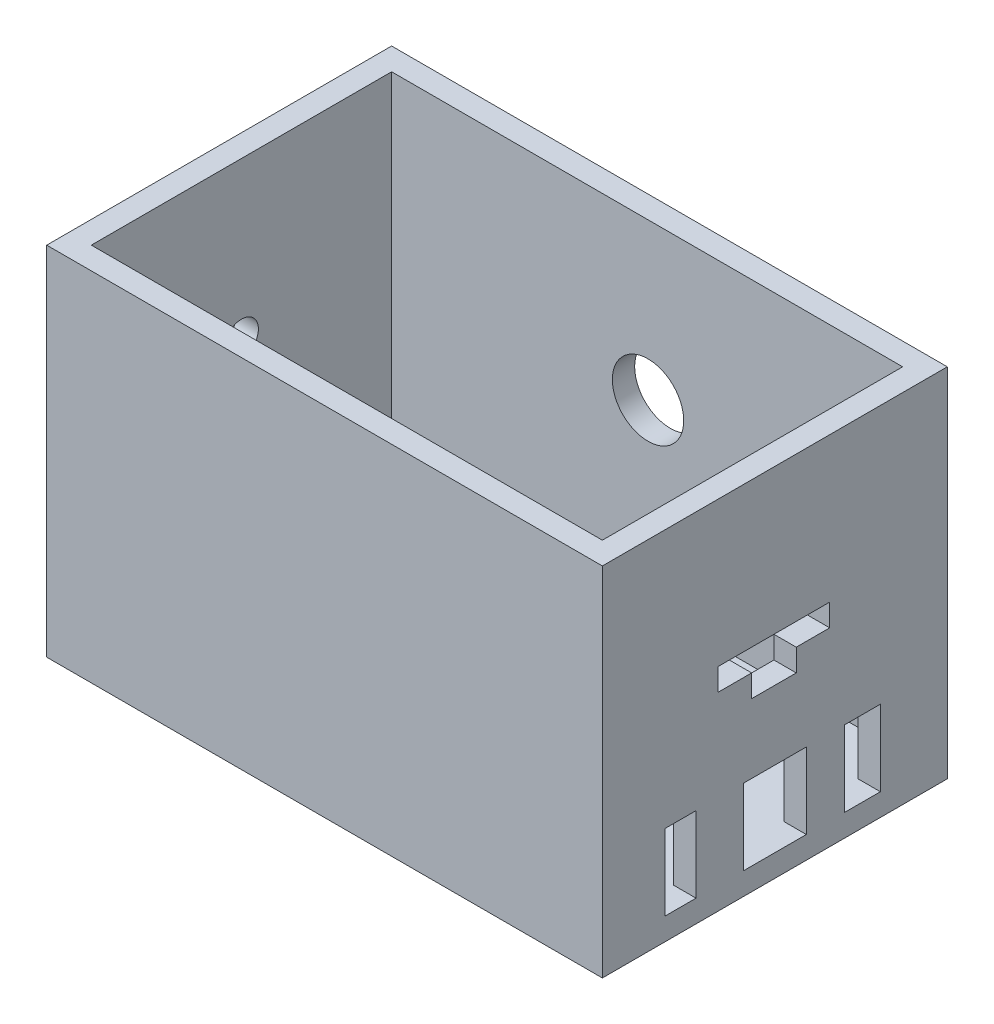
SolidWorks part; units mm, degrees
ref_plane "Front Plane" through (0, 0, 0) normal (0, 0, 1) x (1, 0, 0)
ref_plane "Top Plane" through (0, 0, 0) normal (0, 1, 0) x (1, 0, 0)
ref_plane "Right Plane" through (0, 0, 0) normal (1, 0, 0) x (0, 0, -1)
sketch "Sketch1" plane through (0, 0, 0) normal (0, 1, 0) x (1, 0, 0)
  line L1 (-79.1, 49.1) -> (79.1, 49.1)
  line L2 (-79.1, 49.1) -> (-79.1, -49.1)
  line L3 (-79.1, -49.1) -> (79.1, -49.1)
  line L4 (79.1, 49.1) -> (79.1, -49.1)
  line L5 (-79.1, 49.1) -> (79.1, -49.1) construction
  line L6 (-79.1, -49.1) -> (79.1, 49.1) construction
  point P0 (0, 0)
  dimension "D1" = 158.2
  dimension "D2" = 98.2
extrude "Boss-Extrude1" add sketch "Sketch1" along normal blind 6.35
sketch "Sketch2" plane through (0, 0, 49.1) normal (0, 0, 1) x (1, 0, 0)
  line L1 (-79.1, 101.6) -> (79.1, 101.6)
  line L2 (-79.1, 101.6) -> (-79.1, 6.35)
  line L3 (-79.1, 6.35) -> (79.1, 6.35)
  line L4 (79.1, 101.6) -> (79.1, 6.35)
  line L5 (-79.1, 101.6) -> (79.1, 6.35) construction
  line L6 (-79.1, 6.35) -> (79.1, 101.6) construction
  point P0 (0, 53.975)
  dimension "D1" = 95.25
extrude "Boss-Extrude2" add sketch "Sketch2" against normal blind 6.35
sketch "Sketch3" plane through (-79.1, 0, 0) normal (-1, 0, 0) x (0, 0, 1)
  line L1 (-42.75, 101.6) -> (42.75, 101.6)
  line L2 (-42.75, 101.6) -> (-42.75, 6.35)
  line L3 (-42.75, 6.35) -> (42.75, 6.35)
  line L4 (42.75, 101.6) -> (42.75, 6.35)
  line L5 (-42.75, 101.6) -> (42.75, 6.35) construction
  line L6 (-42.75, 6.35) -> (42.75, 101.6) construction
  point P0 (0, 53.975)
  dimension "D1" = 95.25
extrude "Boss-Extrude3" add sketch "Sketch3" against normal blind 6.35
sketch "Sketch4" plane through (0, 0, -49.1) normal (0, 0, -1) x (-1, 0, 0)
  line L1 (-79.1, 101.6) -> (79.1, 101.6)
  line L2 (-79.1, 101.6) -> (-79.1, 6.35)
  line L3 (-79.1, 6.35) -> (79.1, 6.35)
  line L4 (79.1, 101.6) -> (79.1, 6.35)
  line L5 (-79.1, 101.6) -> (79.1, 6.35) construction
  line L6 (-79.1, 6.35) -> (79.1, 101.6) construction
  point P0 (0, 53.975)
  dimension "D1" = 95.25
extrude "Boss-Extrude4" add sketch "Sketch4" against normal blind 6.35
sketch "Sketch5" plane through (79.1, 0, 0) normal (1, 0, 0) x (0, 0, -1)
  line L0 (42.75, 101.6) -> (42.75, 6.35) construction
  line L1 (-42.75, 27.94) -> (42.75, 27.94)
  line L2 (-42.75, 27.94) -> (-42.75, 101.6)
  line L3 (-42.75, 101.6) -> (42.75, 101.6)
  line L4 (42.75, 27.94) -> (42.75, 101.6)
  line L5 (-42.75, 27.94) -> (42.75, 101.6) construction
  line L6 (-42.75, 101.6) -> (42.75, 27.94) construction
  line L7 (42.75, 101.6) -> (42.75, 6.35) construction
  line L8 (42.75, 101.6) -> (49.1, 101.6) construction
  point P0 (0, 64.77)
  dimension "D1" = 73.66
  dimension "D2" = 0
extrude "Boss-Extrude5" add sketch "Sketch5" against normal blind 6.35
sketch "Sketch6" plane through (79.1, 0, 0) normal (1, 0, 0) x (0, 0, -1)
  line L0 (-42.75, 27.94) -> (42.75, 27.94) construction
  line L1 (-22.43, 27.94) -> (-8.968, 27.94)
  line L2 (-22.43, 27.94) -> (-22.43, 6.35)
  line L3 (-22.43, 6.35) -> (-8.968, 6.35)
  line L4 (-8.968, 27.94) -> (-8.968, 6.35)
  line L5 (-42.75, 6.35) -> (42.75, 6.35) construction
  line L6 (42.75, 6.35) -> (-42.75, 6.35) construction
  line L7 (8.968, 27.94) -> (19.89, 27.94)
  line L8 (8.968, 27.94) -> (8.968, 6.35)
  line L9 (8.968, 6.35) -> (19.89, 6.35)
  line L10 (19.89, 27.94) -> (19.89, 6.35)
  line L11 (-42.75, 6.35) -> (-42.75, 27.94) construction
  line L12 (42.75, 27.94) -> (42.75, 6.35) construction
  line L14 (-42.75, 27.94) -> (-31.32, 27.94)
  line L15 (-42.75, 27.94) -> (-42.75, 6.35)
  line L16 (-42.75, 6.35) -> (-31.32, 6.35)
  line L17 (-31.32, 27.94) -> (-31.32, 6.35)
  line L18 (42.75, 27.94) -> (30.05, 27.94)
  line L19 (42.75, 27.94) -> (42.75, 6.35)
  line L20 (42.75, 6.35) -> (30.05, 6.35)
  line L21 (30.05, 27.94) -> (30.05, 6.35)
  dimension "D1" = 13.462
  dimension "D2" = 10.922
  dimension "D3" = 20.32
  dimension "D4" = 22.86
  dimension "D5" = 0
  dimension "D6" = 11.43
  dimension "D7" = 12.7
  dimension "D8" = 17.936
extrude "Boss-Extrude6" add sketch "Sketch6" against normal blind 6.35
sketch "Çizim2" plane through (79.1, 0, 0) normal (1, 0, 0) x (0, 0, -1)
  line L0 (-49.1, 0) -> (49.1, 0) construction
  line L1 (-16.125, 60.325) -> (15.625, 60.325)
  line L2 (-16.125, 60.325) -> (-16.125, 53.975)
  line L3 (-16.125, 53.975) -> (-6.6, 53.975)
  line L4 (15.625, 60.325) -> (15.625, 53.975)
  line L5 (-16.125, 60.325) -> (15.625, 53.975) construction
  line L6 (-16.125, 53.975) -> (15.625, 60.325) construction
  line L7 (-42.75, 101.6) -> (-42.75, 6.35) construction
  line L8 (6.1, 53.975) -> (15.625, 53.975)
  line L9 (-6.6, 47.625) -> (6.1, 47.625)
  line L10 (-6.6, 47.625) -> (-6.6, 53.975)
  line L12 (6.1, 47.625) -> (6.1, 53.975)
  line L13 (-6.6, 47.625) -> (-0.25, 50.8) construction
  line L14 (-6.6, 53.975) -> (6.1, 47.625) construction
  point P0 (-0.25, 57.15)
  point P9 (-0.25, 50.8)
  dimension "D1" = 60.325
  dimension "D2" = 53.975
  dimension "D3" = 31.75
  dimension "D4" = 42.5
  dimension "D5" = 12.7
  dimension "D6" = 42.5
  dimension "D7" = 6.35
extrude "Kes-Ekstrüzyon1" cut sketch "Çizim2" against normal blind 6.35
sketch "Çizim3" plane through (0, 0, -49.1) normal (0, 0, -1) x (-1, 0, 0)
  line L0 (-79.1, 0) -> (79.1, 0) construction
  line L1 (-79.1, 101.6) -> (-79.1, 0) construction
  circle A0 centre (-0.25, 57.15) radius 10.16
  dimension "D1" = 20.32
  dimension "D2" = 57.15
  dimension "D3" = 78.85
extrude "Kes-Ekstrüzyon2" cut sketch "Çizim3" against normal blind 6.35
sketch "Çizim4" plane through (-79.1, 0, 0) normal (-1, 0, 0) x (0, 0, 1)
  line L0 (-49.1, 0) -> (49.1, 0) construction
  circle A0 centre (0, 57.15) radius 4.826
  dimension "D1" = 57.15
extrude "Kes-Ekstrüzyon3" cut sketch "Çizim4" against normal blind 6.35
